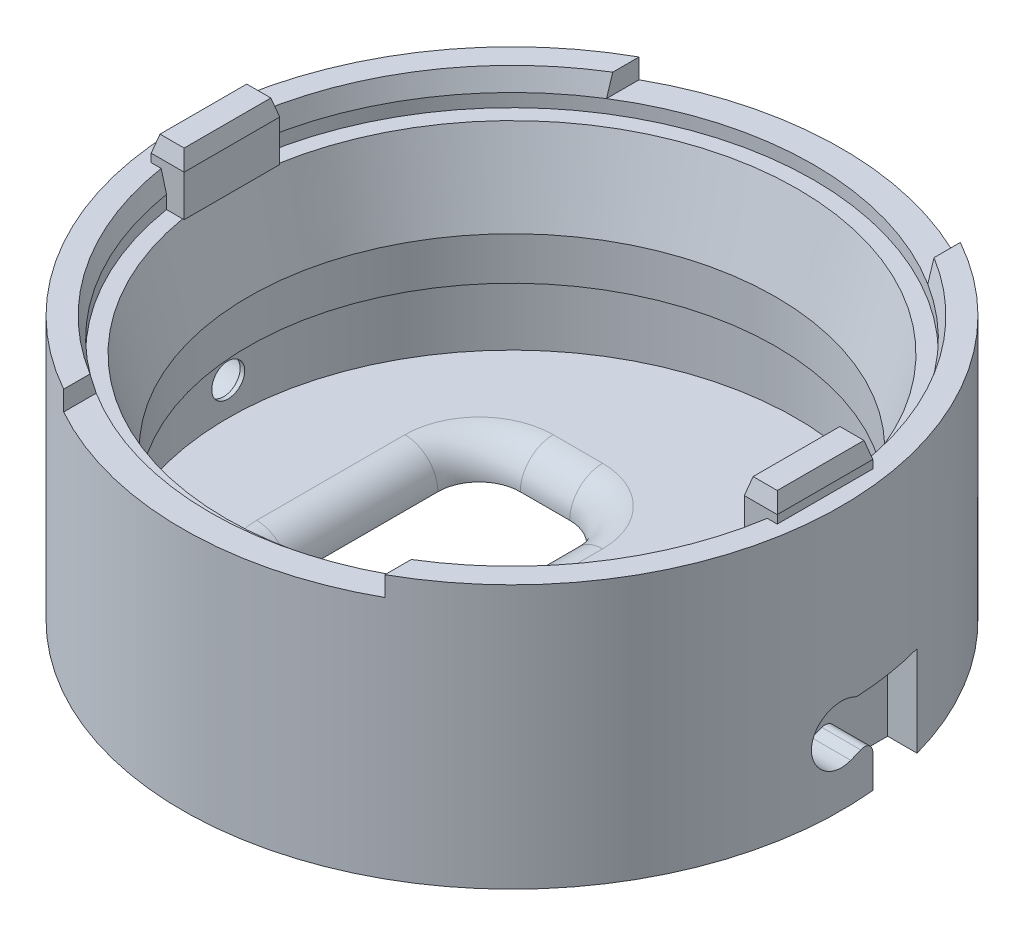
SolidWorks part; units mm, degrees
ref_plane "Ebene vorne" through (0, 0, 0) normal (0, 0, 1) x (1, 0, 0)
ref_plane "Ebene oben" through (0, 0, 0) normal (0, 1, 0) x (1, 0, 0)
ref_plane "Ebene rechts" through (0, 0, 0) normal (1, 0, 0) x (0, 0, -1)
sketch "Skizze1" plane through (0, 0, 0) normal (0, 1, 0) x (1, 0, 0)
  circle A0 centre (0, 0) radius 20
extrude "Aufsatz-Linear austragen1" add sketch "Skizze1" along normal blind 16 contours A0
sketch "Skizze2" plane through (0, 16, 0) normal (0, 1, 0) x (1, 0, 0)
  circle A0 centre (0, 0) radius 16
extrude "Schnitt-Linear austragen1" cut sketch "Skizze2" against normal blind 14
ref_plane "Ebene1" through (-20, 0, 0) normal (1, 0, 0) x (0, 0, -1)
sketch "Skizze3" plane through (-20, 0, -20) normal (-1, 0, 0) x (0, 0, 1)
  line L0 (0, 0) -> (40, 0) construction
  line L2 (22, 2.8402) -> (22, 0)
  line L3 (22, 0) -> (25.3, 0)
  line L4 (25.3, 5.5) -> (25.3, 0)
  line L5 (20.5722, 2.3462) -> (22, 2.8402)
  line L8 (25.3, 5.5) -> (20.9014, 5.5)
  line L10 (20, 10.28) -> (20, 0) construction
  arc A0 (20.9014, 5.5) -> (20.5722, 2.3462) centre (20, 4) ccw
  dimension "D1" = 4
  dimension "D3" = 3.5
  dimension "D2" = 3.3
  dimension "D4" = 0
  dimension "D5" = 5.5
  dimension "D6" = 2
extrude "Schnitt-Linear austragen4" cut sketch "Skizze3" against normal blind 2.5
sketch "Skizze12" plane through (-17.5, 0, 0) normal (-1, 0, 0) x (0, 0, 1)
  circle A0 centre (0, 4) radius 1
extrude "Schnitt-Linear austragen9" cut sketch "Skizze12" against normal blind 2
sketch "Skizze16" plane through (-17.5, 0, 0) normal (-1, 0, 0) x (0, 0, 1)
  line L0 (2, 0) -> (5.3, 0) construction
  line L1 (2.0699, 0) -> (-2.4393, 0)
  line L2 (2.0699, 0) -> (2.0699, 2.8586)
  line L3 (2.0699, 2.8586) -> (-2.4393, 2.8586)
  line L4 (-2.4393, 0) -> (-2.4393, 2.8586)
extrude "Schnitt-Linear austragen13" cut sketch "Skizze16" along normal blind 0.1
pattern_circular "Kreismuster1" count 2 over 360 about axis through (0, 0, 0) along (0, 1, 0) of "Schnitt-Linear austragen4", "Schnitt-Linear austragen9", "Schnitt-Linear austragen13"
sketch "Skizze5" plane through (0, 2, 0) normal (0, 1, 0) x (1, 0, 0)
  circle A0 centre (0, 0) radius 17.25
extrude "Schnitt-Linear austragen5" cut sketch "Skizze5" along normal blind 4.4 contours A0
fillet "Verrundung3" radius 0.6 7 edges at (-18.7499, 2.8402, 2) (18.7499, 2.8402, -2) (18.7398, 5.5, -0.9014) (-18.7398, 5.5, 0.9014) (-18.3925, 5.5, 5.3) (-18.3925, 0, 5.3) (-18.7499, 0, 2) tangent propagation no
sketch "Skizze6" plane through (0, 2, 0) normal (0, 1, 0) x (1, 0, 0)
  circle A0 centre (0, 7.55) radius 2.2
  circle A1 centre (0, -7.55) radius 2.2
sketch "Skizze8" plane through (0, 2, 0) normal (0, 1, 0) x (1, 0, 0)
  line L0 (0, 0) -> (-25.3009, 0) construction
  line L1 (-3.5, 7) -> (-6.5, 7)
  line L2 (-1, 4.5) -> (-1, -4.5)
  line L3 (-3.5, -7) -> (-6.5, -7)
  line L4 (-9, 4.5) -> (-9, -4.5)
  arc A0 (-6.5, 7) -> (-9, 4.5) centre (-6.5, 4.5) ccw
  arc A1 (-1, 4.5) -> (-3.5, 7) centre (-3.5, 4.5) ccw
  arc A2 (-3.5, -7) -> (-1, -4.5) centre (-3.5, -4.5) ccw
  arc A3 (-6.5, -7) -> (-9, -4.5) centre (-6.5, -4.5) cw
  circle A4 centre (8.1403, 0) radius 5
  point P9 (-9, 7)
  point P14 (-1, -7)
  point P17 (-9, -7)
  dimension "D5" = 2.5
  dimension "D1" = 8
  dimension "D2" = 14
  dimension "D3" = 7
  dimension "D4" = 1
extrude "Schnitt-Linear austragen7" cut sketch "Skizze8" against normal blind 4
sketch "Skizze9" plane through (0, 16, 0) normal (0, 1, 0) x (1, 0, 0)
  circle A0 centre (0, 0) radius 18.3
extrude "Schnitt-Linear austragen8" cut sketch "Skizze9" against normal blind 2 contours A0
chamfer "Fase4" distance 1.2 angle 15 1 edges at (0, 16, 18.3) first distance on face at (0, 14, 18.3)
chamfer "Fase7" distance 5 angle 15 1 edges at (0, 14, 16) first distance on face at (0, 6.4, 16)
sketch "Skizze14" plane through (0, 16, 0) normal (0, 1, 0) x (1, 0, 0)
  line L1 (9.75, -20.9943) -> (-9.75, -20.9943)
  line L2 (9.75, -20.9943) -> (9.75, 21.7865)
  line L3 (9.75, 21.7865) -> (-9.75, 21.7865)
  line L4 (-9.75, -20.9943) -> (-9.75, 21.7865)
  dimension "D1" = 19.5
  dimension "D2" = 9.75
extrude "Schnitt-Linear austragen12" cut sketch "Skizze14" against normal blind 1.2 contours L4 L3 L2 L1
fillet "Verrundung4" radius 2 9 edges at (-1.7322, 2, -6.2678) (-5, 2, -7) (-8.2678, 2, -6.2678) (-9, 2, 0) (-8.2678, 2, 6.2678) (-5, 2, 7) (-1.7322, 2, 6.2678) (-1, 2, 0) (8.1403, 2, 5)
sketch "Skizze15" plane through (0, 14, 0) normal (0, 1, 0) x (1, 0, 0)
  line L0 (0, 0) -> (-27.2438, 0) construction
  line L1 (-19, 2.9) -> (-17, 2.9)
  line L2 (-19, 2.9) -> (-19, -2.9)
  line L3 (-19, -2.9) -> (-17, -2.9)
  line L4 (-17, 2.9) -> (-17, -2.9)
  dimension "D1" = 2
  dimension "D2" = 5.8
  dimension "D3" = 2.9
  dimension "D4" = 17
extrude "Aufsatz-Linear austragen7" add sketch "Skizze15" along normal blind 3.5 contours L4 L3 L2 L1
chamfer "Fase8" distance 1 angle 15 4 edges at (-17, 17.5, 0) (-18, 17.5, 2.9) (-19, 17.5, 0) (-18, 17.5, -2.9) first distance on face at (-17, 15.75, 0) first distance on face at (-17.9331, 15.4, 2.9) first distance on face at (-19, 16.75, 0) first distance on face at (-17.9331, 15.4, -2.9)
pattern_circular "Kreismuster2" count 2 over 360 about axis through (0, 9, 0) along (0, 1, 0) of "Aufsatz-Linear austragen7", "Fase8"
